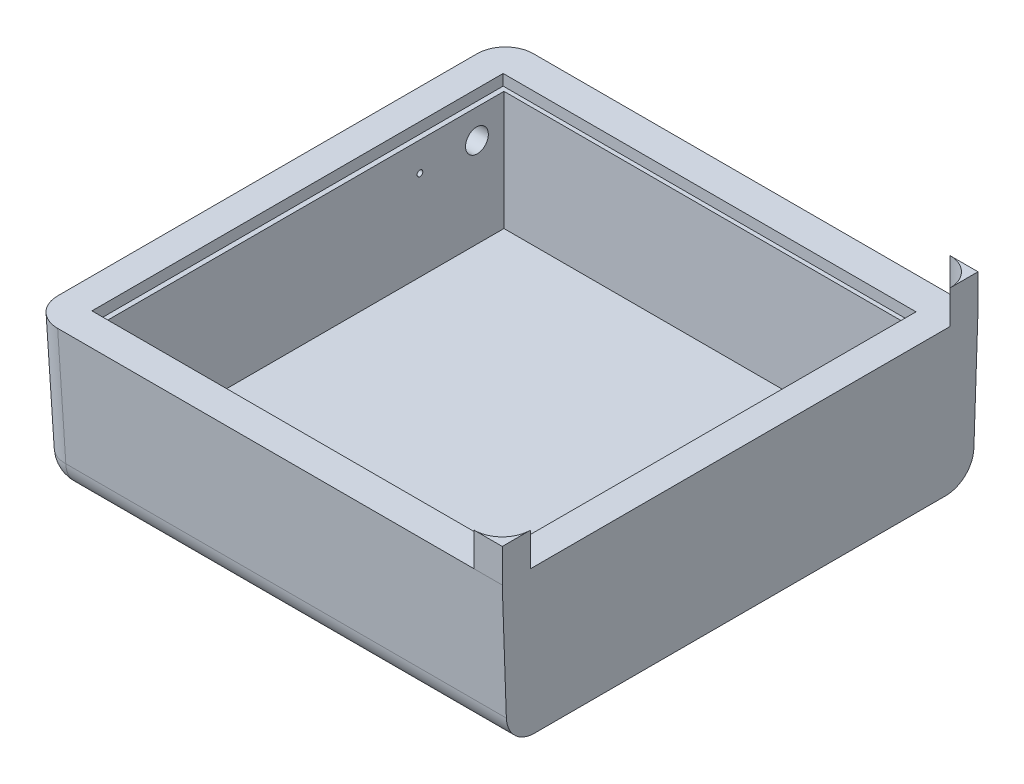
SolidWorks part; units mm, degrees
ref_plane "Front Plane" through (0, 0, 0) normal (0, 0, 1) x (1, 0, 0)
ref_plane "Top Plane" through (0, 0, 0) normal (0, 1, 0) x (1, 0, 0)
ref_plane "Right Plane" through (0, 0, 0) normal (1, 0, 0) x (0, 0, -1)
sketch "Sketch1" plane through (0, 0, 0) normal (0, 1, 0) x (1, 0, 0)
  line L1 (-145.25, -146.05) -> (149.75, -146.05)
  line L2 (-145.25, -146.05) -> (-145.25, 146.05)
  line L3 (-145.25, 146.05) -> (149.75, 146.05)
  line L4 (149.75, -146.05) -> (149.75, 146.05)
  point P0 (-145.25, 0)
  dimension "D1" = 145.25
  dimension "D3" = 292.1
  dimension "D5" = 295
extrude "Boss-Extrude1" add sketch "Sketch1" against normal blind 88.69 draft 2
sketch "Sketch3" plane through (0, 0, 0) normal (0, 1, 0) x (1, 0, 0)
  line L1 (-126.75, -126.25) -> (126.75, -126.25)
  line L4 (126.75, 126.25) -> (126.75, -126.25)
  line L9 (-126.75, 126.25) -> (-126.75, -126.25)
  line L183 (-126.75, 126.25) -> (126.75, 126.25)
  point P1 (-126.75, 0)
  dimension "D2" = 253.5
  dimension "D3" = 126.75
  dimension "D1" = 252.5
extrude "Cut-Extrude3" cut sketch "Sketch3" against normal blind 6.5 draft 2
sketch "Sketch5" plane through (0, -6.5, 0) normal (0, 1, 0) x (1, 0, 0)
  line L1 (-123.5, -123.5) -> (123.5, -123.5)
  line L2 (-123.5, -123.5) -> (-123.5, 123.5)
  line L3 (-123.5, 123.5) -> (123.5, 123.5)
  line L4 (123.5, -123.5) -> (123.5, 123.5)
  line L5 (-123.5, -123.5) -> (123.5, 123.5) construction
  line L6 (-123.5, 123.5) -> (123.5, -123.5) construction
  point P0 (0, 0)
  dimension "D1" = 247
extrude "Cut-Extrude4" cut sketch "Sketch5" against normal blind 70.5 draft 2
sketch "Sketch6" plane through (0, 0, 0) normal (0, 0, 1) x (1, 0, 0)
  line L0 (149.75, 0) -> (145, 0)
  line L1 (-145.25, 0) -> (149.75, 0) construction
  line L2 (145, 0) -> (145, -88.69)
  line L3 (-142.1529, -88.69) -> (146.6529, -88.69) construction
  line L4 (145, -88.69) -> (146.6529, -88.69)
  line L5 (146.6529, -88.69) -> (149.75, 0)
  dimension "D1" = 4.75
extrude "Cut-Extrude5" cut sketch "Sketch6" against normal through all both and the other way through all
fillet "Fillet2" radius 17.27 5 edges at (1.4236, -88.69, -142.9529) (-143.7014, -44.345, -144.5014) (-142.1529, -88.69, 0) (-143.7014, -44.345, 144.5014) (1.4236, -88.69, 142.9529)
sketch "Sketch7" plane through (0, 0, 0) normal (0, 1, 0) x (1, 0, 0)
  line L0 (-31.4885, 0) -> (69.7112, 0) construction
  line L1 (145, 146.05) -> (-127.9905, 146.05) construction
  line L2 (145, 146.05) -> (145, -146.05) construction
  line L3 (145, 128.78) -> (145, 146.05)
  line L4 (145, 146.05) -> (127.73, 146.05)
  line L5 (145, -146.05) -> (127.73, -146.05)
  line L6 (145, -128.78) -> (145, -146.05)
  arc A0 (127.73, 146.05) -> (145, 128.78) centre (127.73, 128.78) cw
  arc A1 (127.73, -146.05) -> (145, -128.78) centre (127.73, -128.78) ccw
  dimension "D1" = 17.27
extrude "Boss-Extrude2" add sketch "Sketch7" along normal blind 20.53
sketch "Sketch8" plane through (-145.0731, -5.0661, 0) normal (-0.9994, -0.0349, 0) x (0, 0, 1)
  line L0 (-128.7905, 5.0692) -> (128.7905, 5.0692) construction
  line L2 (-76, -22.2508) -> (-66.6, -22.2508)
  line L3 (-123.5, -10.8061) -> (-123.5, -2.186) construction
  line L4 (-77, -21.2508) -> (-77, -17.5508)
  line L5 (-76, -16.5508) -> (-66.6, -16.5508)
  line L6 (-65.6, -21.2508) -> (-65.6, -17.5508)
  line L7 (-77, -22.2508) -> (-65.6, -16.5508) construction
  line L8 (-77, -16.5508) -> (-65.6, -22.2508) construction
  circle A0 centre (-106.3, -19.4008) radius 7
  arc A1 (-66.6, -16.5508) -> (-65.6, -17.5508) centre (-66.6, -17.5508) cw
  arc A2 (-66.6, -22.2508) -> (-65.6, -21.2508) centre (-66.6, -21.2508) ccw
  arc A3 (-76, -22.2508) -> (-77, -21.2508) centre (-76, -21.2508) cw
  arc A4 (-77, -17.5508) -> (-76, -16.5508) centre (-76, -17.5508) cw
  point P4 (-71.3, -19.4008)
  dimension "D3" = 14
  dimension "D5" = 1
  dimension "D1" = 24.47
  dimension "D2" = 17.2
  dimension "D4" = 35
  dimension "D6" = 9.4
  dimension "D7" = 3.7
extrude "Cut-Extrude6" cut sketch "Sketch8" against normal up to next contours A0 region at (-144.396, -24.4551, -106.3)
extrude "Cut-Extrude7" cut sketch "Sketch8<3>" against normal blind 5 contours A4 L4 A3 L2 A2 L6 A1 L5 region at (-144.396, -24.4551, -71.3)
sketch "Sketch8<3>" plane through (-145.0731, -5.0661, 0) normal (-0.9994, -0.0349, 0) x (0, 0, 1) same geometry as "Sketch8"
sketch "Sketch9" plane through (-140.0761, -4.8916, 0) normal (-0.9994, -0.0349, 0) x (0, 0, 1)
  line L2 (-65.6, -21.2508) -> (-65.6, -17.5508) construction
  line L3 (-76, -22.2508) -> (-66.6, -22.2508) construction
  circle A0 centre (-71.3, -19.4008) radius 1.75
  point P8 (-65.6, -19.4008)
  point P10 (-71.3, -22.2508)
  dimension "D1" = 3.5
extrude "Cut-Extrude8" cut sketch "Sketch9" against normal up to next
